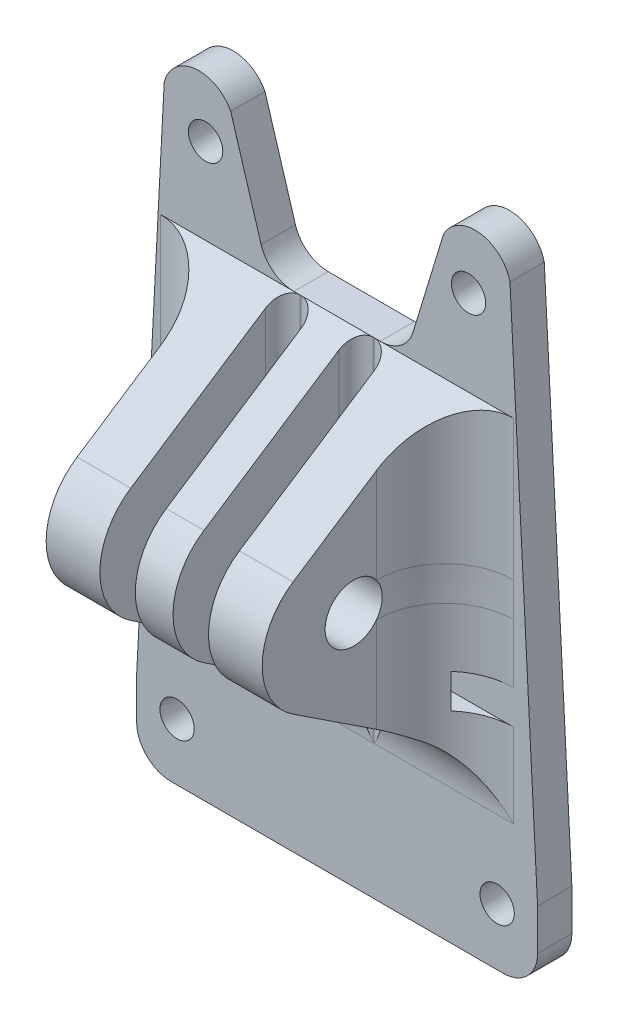
SolidWorks part; units mm, degrees
ref_plane "Alzado" through (0, 0, 0) normal (0, 0, 1) x (1, 0, 0)
ref_plane "Planta" through (0, 0, 0) normal (0, 1, 0) x (1, 0, 0)
ref_plane "Vista lateral" through (0, 0, 0) normal (1, 0, 0) x (0, 0, -1)
sketch "Croquis1" plane through (0, 0, 0) normal (0, 0, 1) x (1, 0, 0)
  line L0 (0, 0) -> (27.8544, 27.8544) construction
  line L1 (0, 0) -> (-42.4264, 42.4264) construction
  line L2 (0, 0) -> (0, 42.4264) construction
  line L3 (15.25, -15.25) -> (-15.25, -15.25) construction
  line L4 (15.25, -15.25) -> (15.25, 15.25) construction
  line L5 (15.25, 15.25) -> (-15.25, 15.25) construction
  line L6 (-15.25, -15.25) -> (-15.25, 15.25) construction
  line L7 (15.25, -15.25) -> (-15.25, 15.25) construction
  line L8 (15.25, 15.25) -> (-15.25, -15.25) construction
  line L9 (0, 42.4264) -> (-20, 42.4264) construction
  line L10 (-42.4264, 42.4264) -> (-38.8909, 45.9619) construction
  line L11 (-38.8909, 45.9619) -> (-31.0962, 38.1673) construction
  line L13 (-42.4264, 42.4264) -> (-45.9619, 38.8909) construction
  line L14 (-45.9619, 38.8909) -> (-38.1673, 31.0962) construction
  line L16 (38.8909, 45.9619) -> (31.0962, 38.1673) construction
  line L17 (42.4264, 42.4264) -> (38.8909, 45.9619) construction
  line L18 (42.4264, 42.4264) -> (45.9619, 38.8909) construction
  line L19 (-45.9619, -38.8909) -> (-38.1673, -31.0962) construction
  line L20 (0, 0) -> (-15.25, 0) construction
  line L21 (45.9619, 38.8909) -> (38.1673, 31.0962) construction
  line L22 (42.4264, -42.4264) -> (45.9619, -38.8909) construction
  line L23 (42.4264, -42.4264) -> (38.8909, -45.9619) construction
  line L24 (38.8909, -45.9619) -> (31.0962, -38.1673) construction
  line L27 (-38.8909, -45.9619) -> (-31.0962, -38.1673) construction
  line L28 (-42.4264, -42.4264) -> (-38.8909, -45.9619) construction
  line L29 (-42.4264, -42.4264) -> (-45.9619, -38.8909) construction
  line L30 (45.9619, -38.8909) -> (38.1673, -31.0962) construction
  line L31 (-15, 80) -> (15, 80) construction
  line L32 (0, -15.25) -> (0, -80) construction
  line L36 (-15, -80) -> (15, -80) construction
  line L41 (-12.268, -54) -> (-12.268, -67.5) construction
  line L43 (-10.268, -54) -> (-10.268, -67.5) construction
  line L105 (0, -80) -> (0, -83) construction
  line L106 (-15, -80) -> (0, -83) construction
  line L127 (15, -80) -> (0, -83) construction
  line L131 (0, 80) -> (0, 83) construction
  line L132 (-15, 80) -> (15, 80) construction
  line L136 (15, 80) -> (0, 83) construction
  line L157 (-15, 80) -> (0, 83) construction
  line L160 (-14, 30) -> (-17.8891, 33.8891) construction
  line L161 (-31.0962, 38.1673) -> (-22.6531, 29.7242) construction
  line L162 (-17.5359, 31.6883) -> (-15, 80) construction
  line L163 (17.5359, 31.6883) -> (15, 80) construction
  line L164 (31.0962, 38.1673) -> (22.6531, 29.7242) construction
  line L165 (31.0962, -38.1673) -> (22.6531, -29.7242) construction
  line L166 (17.5359, -31.6883) -> (15, -80) construction
  line L167 (-17.5359, -31.6883) -> (-15, -80) construction
  line L168 (-31.0962, -38.1673) -> (-22.6531, -29.7242) construction
  line L169 (-8.268, -54) -> (-8.268, -67.5) construction
  line L170 (-6.268, -54) -> (-6.268, -67.5) construction
  line L171 (-4.268, -54) -> (-4.268, -67.5) construction
  line L172 (-2.268, -54) -> (-2.268, -67.5) construction
  line L173 (-8.268, -35) -> (-8.268, -48.5) construction
  line L174 (-6.268, -35) -> (-6.268, -48.5) construction
  line L175 (-4.268, -35) -> (-4.268, -48.5) construction
  line L176 (-2.268, -35) -> (-2.268, -48.5) construction
  line L177 (-12.268, -35) -> (-12.268, -48.5) construction
  line L178 (-10.268, -35) -> (-10.268, -48.5) construction
  line L179 (10.268, -35) -> (10.268, -48.5) construction
  line L180 (12.268, -35) -> (12.268, -48.5) construction
  line L181 (2.268, -35) -> (2.268, -48.5) construction
  line L182 (4.268, -35) -> (4.268, -48.5) construction
  line L183 (6.268, -35) -> (6.268, -48.5) construction
  line L184 (8.268, -35) -> (8.268, -48.5) construction
  line L185 (2.268, -54) -> (2.268, -67.5) construction
  line L186 (4.268, -54) -> (4.268, -67.5) construction
  line L187 (6.268, -54) -> (6.268, -67.5) construction
  line L188 (8.268, -54) -> (8.268, -67.5) construction
  line L189 (10.268, -54) -> (10.268, -67.5) construction
  line L190 (12.268, -54) -> (12.268, -67.5) construction
  line L191 (12.268, 54) -> (12.268, 67.5) construction
  line L192 (10.268, 54) -> (10.268, 67.5) construction
  line L193 (8.268, 54) -> (8.268, 67.5) construction
  line L194 (6.268, 54) -> (6.268, 67.5) construction
  line L195 (4.268, 54) -> (4.268, 67.5) construction
  line L196 (2.268, 54) -> (2.268, 67.5) construction
  line L197 (8.268, 35) -> (8.268, 48.5) construction
  line L198 (6.268, 35) -> (6.268, 48.5) construction
  line L199 (4.268, 35) -> (4.268, 48.5) construction
  line L200 (2.268, 35) -> (2.268, 48.5) construction
  line L201 (12.268, 35) -> (12.268, 48.5) construction
  line L202 (10.268, 35) -> (10.268, 48.5) construction
  line L203 (-10.268, 35) -> (-10.268, 48.5) construction
  line L204 (-12.268, 35) -> (-12.268, 48.5) construction
  line L205 (-2.268, 35) -> (-2.268, 48.5) construction
  line L206 (-4.268, 35) -> (-4.268, 48.5) construction
  line L207 (-6.268, 35) -> (-6.268, 48.5) construction
  line L208 (-8.268, 35) -> (-8.268, 48.5) construction
  line L209 (-2.268, 54) -> (-2.268, 67.5) construction
  line L210 (-4.268, 54) -> (-4.268, 67.5) construction
  line L211 (-6.268, 54) -> (-6.268, 67.5) construction
  line L212 (-8.268, 54) -> (-8.268, 67.5) construction
  line L213 (-10.268, 54) -> (-10.268, 67.5) construction
  line L214 (-12.268, 54) -> (-12.268, 67.5) construction
  line L215 (-0.621, -15.7817) -> (-8.2129, -22.282) construction
  line L216 (-7.5625, -24.0416) -> (8.3607, -24.0416) construction
  line L217 (8.9758, -22.2532) -> (0.6445, -15.7529) construction
  line L218 (-7.5625, 24.0416) -> (8.3607, 24.0416) construction
  line L219 (8.9758, 22.2532) -> (0.6445, 15.7529) construction
  line L220 (-0.621, 15.7817) -> (-8.2129, 22.282) construction
  line L221 (-38.1673, 31.0962) -> (-28.2843, 21.2132) construction
  line L222 (-28.2843, -21.2132) -> (-38.1673, -31.0962) construction
  line L223 (28.2843, -21.2132) -> (38.1673, -31.0962) construction
  line L224 (38.1673, 31.0962) -> (28.2843, 21.2132) construction
  line L225 (-17.5359, 31.6883) -> (-15, 80)
  line L226 (-15, 80) -> (0, 83)
  line L227 (0, 83) -> (15, 80)
  line L228 (15, 80) -> (17.5359, 31.6883)
  line L229 (17.5359, 31.6883) -> (17.5359, -31.6883)
  line L230 (17.5359, -31.6883) -> (15, -80)
  line L231 (15, -80) -> (0, -83)
  line L232 (0, -83) -> (-15, -80)
  line L233 (-15, -80) -> (-17.5359, -31.6883)
  line L234 (-17.5359, -31.6883) -> (-17.5359, 31.6883)
  circle A0 centre (-15.25, 15.25) radius 4 construction
  circle A1 centre (-24.0416, 24.0416) radius 1.5 construction
  circle A2 centre (-38.8909, 38.8909) radius 1.5 construction
  circle A5 centre (38.8909, 38.8909) radius 1.5 construction
  circle A6 centre (24.0416, 24.0416) radius 1.5 construction
  circle A7 centre (15.25, 15.25) radius 4 construction
  circle A8 centre (15.25, -15.25) radius 4 construction
  circle A9 centre (24.0416, -24.0416) radius 1.5 construction
  circle A10 centre (38.8909, -38.8909) radius 1.5 construction
  circle A12 centre (-15.25, -15.25) radius 4 construction
  circle A13 centre (-24.0416, -24.0416) radius 1.5 construction
  circle A14 centre (-38.8909, -38.8909) radius 1.5 construction
  circle A18 centre (0, 0) radius 3.5 construction
  circle A19 centre (-11.5, -75) radius 1.5 construction
  circle A21 centre (-14, 30) radius 1.5 construction
  arc A27 (-12.268, -54) -> (-10.268, -54) centre (-11.268, -54) cw construction
  arc A28 (-12.268, -67.5) -> (-10.268, -67.5) centre (-11.268, -67.5) ccw construction
  circle A111 centre (11.5, -75) radius 1.5 construction
  circle A112 centre (11.5, 75) radius 1.5 construction
  circle A137 centre (-11.5, 75) radius 1.5 construction
  arc A138 (-22.6531, 29.7242) -> (-17.5359, 31.6883) centre (-20.5318, 31.8455) ccw construction
  arc A139 (22.6531, 29.7242) -> (17.5359, 31.6883) centre (20.5318, 31.8455) cw construction
  arc A140 (22.6531, -29.7242) -> (17.5359, -31.6883) centre (20.5318, -31.8455) ccw construction
  arc A141 (-22.6531, -29.7242) -> (-17.5359, -31.6883) centre (-20.5318, -31.8455) cw construction
  circle A142 centre (14, 30) radius 1.5 construction
  circle A143 centre (14, -30) radius 1.5 construction
  circle A144 centre (-14, -30) radius 1.5 construction
  arc A145 (-8.268, -67.5) -> (-6.268, -67.5) centre (-7.268, -67.5) ccw construction
  arc A146 (-8.268, -54) -> (-6.268, -54) centre (-7.268, -54) cw construction
  arc A147 (-4.268, -67.5) -> (-2.268, -67.5) centre (-3.268, -67.5) ccw construction
  arc A148 (-4.268, -54) -> (-2.268, -54) centre (-3.268, -54) cw construction
  arc A149 (-8.268, -48.5) -> (-6.268, -48.5) centre (-7.268, -48.5) ccw construction
  arc A150 (-8.268, -35) -> (-6.268, -35) centre (-7.268, -35) cw construction
  arc A151 (-4.268, -48.5) -> (-2.268, -48.5) centre (-3.268, -48.5) ccw construction
  arc A152 (-4.268, -35) -> (-2.268, -35) centre (-3.268, -35) cw construction
  arc A153 (-12.268, -48.5) -> (-10.268, -48.5) centre (-11.268, -48.5) ccw construction
  arc A154 (-12.268, -35) -> (-10.268, -35) centre (-11.268, -35) cw construction
  arc A155 (12.268, -35) -> (10.268, -35) centre (11.268, -35) ccw construction
  arc A156 (12.268, -48.5) -> (10.268, -48.5) centre (11.268, -48.5) cw construction
  arc A157 (4.268, -35) -> (2.268, -35) centre (3.268, -35) ccw construction
  arc A158 (4.268, -48.5) -> (2.268, -48.5) centre (3.268, -48.5) cw construction
  arc A159 (8.268, -35) -> (6.268, -35) centre (7.268, -35) ccw construction
  arc A160 (8.268, -48.5) -> (6.268, -48.5) centre (7.268, -48.5) cw construction
  arc A161 (4.268, -54) -> (2.268, -54) centre (3.268, -54) ccw construction
  arc A162 (4.268, -67.5) -> (2.268, -67.5) centre (3.268, -67.5) cw construction
  arc A163 (8.268, -54) -> (6.268, -54) centre (7.268, -54) ccw construction
  arc A164 (8.268, -67.5) -> (6.268, -67.5) centre (7.268, -67.5) cw construction
  arc A165 (12.268, -67.5) -> (10.268, -67.5) centre (11.268, -67.5) cw construction
  arc A166 (12.268, -54) -> (10.268, -54) centre (11.268, -54) ccw construction
  arc A167 (12.268, 54) -> (10.268, 54) centre (11.268, 54) cw construction
  arc A168 (12.268, 67.5) -> (10.268, 67.5) centre (11.268, 67.5) ccw construction
  arc A169 (8.268, 67.5) -> (6.268, 67.5) centre (7.268, 67.5) ccw construction
  arc A170 (8.268, 54) -> (6.268, 54) centre (7.268, 54) cw construction
  arc A171 (4.268, 67.5) -> (2.268, 67.5) centre (3.268, 67.5) ccw construction
  arc A172 (4.268, 54) -> (2.268, 54) centre (3.268, 54) cw construction
  arc A173 (8.268, 48.5) -> (6.268, 48.5) centre (7.268, 48.5) ccw construction
  arc A174 (8.268, 35) -> (6.268, 35) centre (7.268, 35) cw construction
  arc A175 (4.268, 48.5) -> (2.268, 48.5) centre (3.268, 48.5) ccw construction
  arc A176 (4.268, 35) -> (2.268, 35) centre (3.268, 35) cw construction
  arc A177 (12.268, 48.5) -> (10.268, 48.5) centre (11.268, 48.5) ccw construction
  arc A178 (12.268, 35) -> (10.268, 35) centre (11.268, 35) cw construction
  arc A179 (-12.268, 35) -> (-10.268, 35) centre (-11.268, 35) ccw construction
  arc A180 (-12.268, 48.5) -> (-10.268, 48.5) centre (-11.268, 48.5) cw construction
  arc A181 (-4.268, 35) -> (-2.268, 35) centre (-3.268, 35) ccw construction
  arc A182 (-4.268, 48.5) -> (-2.268, 48.5) centre (-3.268, 48.5) cw construction
  arc A183 (-8.268, 35) -> (-6.268, 35) centre (-7.268, 35) ccw construction
  arc A184 (-8.268, 48.5) -> (-6.268, 48.5) centre (-7.268, 48.5) cw construction
  arc A185 (-4.268, 54) -> (-2.268, 54) centre (-3.268, 54) ccw construction
  arc A186 (-4.268, 67.5) -> (-2.268, 67.5) centre (-3.268, 67.5) cw construction
  arc A187 (-8.268, 54) -> (-6.268, 54) centre (-7.268, 54) ccw construction
  arc A188 (-8.268, 67.5) -> (-6.268, 67.5) centre (-7.268, 67.5) cw construction
  arc A189 (-12.268, 67.5) -> (-10.268, 67.5) centre (-11.268, 67.5) cw construction
  arc A190 (-12.268, 54) -> (-10.268, 54) centre (-11.268, 54) ccw construction
  arc A191 (8.3607, -24.0416) -> (8.9758, -22.2532) centre (8.3607, -23.0416) ccw construction
  arc A192 (0.6445, -15.7529) -> (-0.621, -15.7817) centre (0.0294, -16.5413) ccw construction
  arc A193 (-8.2129, -22.282) -> (-7.5625, -24.0416) centre (-7.5625, -23.0416) ccw construction
  arc A194 (8.3607, 24.0416) -> (8.9758, 22.2532) centre (8.3607, 23.0416) cw construction
  arc A195 (0.6445, 15.7529) -> (-0.621, 15.7817) centre (0.0294, 16.5413) cw construction
  arc A196 (-8.2129, 22.282) -> (-7.5625, 24.0416) centre (-7.5625, 23.0416) cw construction
  arc A197 (-28.2843, 21.2132) -> (-28.2843, -21.2132) centre (-49.4975, 0) cw construction
  arc A198 (28.2843, 21.2132) -> (28.2843, -21.2132) centre (49.4975, 0) ccw construction
  circle A199 centre (-11.5, 75) radius 1.5
  circle A200 centre (11.5, 75) radius 1.5
  circle A201 centre (14, 30) radius 1.5
  circle A202 centre (-14, 30) radius 1.5
  circle A203 centre (-14, -30) radius 1.5
  circle A204 centre (14, -30) radius 1.5
  circle A205 centre (-11.5, -75) radius 1.5
  circle A206 centre (11.5, -75) radius 1.5
  point P35 (-34.9935, 42.0646)
  point P37 (44.1942, 40.6586)
  point P45 (44.1942, -40.6586)
  point P52 (-16.268, -55.8441)
  point P61 (-34.9935, -42.0646)
  point P70 (0, 80)
  point P260 (-7.0711, 0)
  dimension "D2" = 8
  dimension "D4" = 5
  dimension "D8" = 14.75
  dimension "D10" = 3
  dimension "D11" = 3
  dimension "D13" = 11.5
  dimension "D15" = 3
  dimension "D16" = 14
  dimension "D18" = 3
  dimension "D24" = 3
  dimension "D26" = 1
  dimension "D27" = 7
  dimension "D28" = 30
  dimension "D1" = 30.5
  dimension "D3" = 60
  dimension "D5" = 21
  dimension "D6" = 15
  dimension "D7" = 5
  dimension "D9" = 5
  dimension "D12" = 80
  dimension "D14" = 5
  dimension "D17" = 4
  dimension "D19" = 2
  dimension "D20" = 13.5
  dimension "D21" = 7.5
  dimension "D22" = 3
  dimension "D25" = 2
  dimension "D23" = 5.5
extrude "Saliente-Extruir1" add sketch "Croquis1" along normal blind 2
sketch "Croquis2" plane through (0, 0, 2) normal (0, 0, 1) x (1, 0, 0)
  line L1 (0, 83) -> (-15, 80) construction
  line L2 (-7.5, 81.5) -> (7.5, 81.5) construction
  line L3 (15, 80) -> (0, 83) construction
  line L4 (7.5, 81.5) -> (15, 80) construction
  line L5 (0, 81.5) -> (0, 67.5) construction
  line L6 (-10, 75) -> (-8.2794, 75) construction
  line L7 (-10.0971, 80.9806) -> (-8.2794, 75) construction
  line L8 (-10.0971, 80.9806) -> (-6, 67.5)
  line L9 (-6, 67.5) -> (6, 67.5)
  line L10 (-10.0971, 80.9806) -> (0, 83)
  line L11 (10.0971, 80.9806) -> (6, 67.5)
  line L12 (10.0971, 80.9806) -> (0, 83)
  line L13 (-10, 75) -> (-10, 65) construction
  line L14 (-10, 65) -> (-11.3105, 40.0344)
  line L15 (0, 67.5) -> (0, 30) construction
  line L16 (-10.6552, 52.5172) -> (0, 51.9579) construction
  line L17 (0, 51.9579) -> (-2, 52.0629) construction
  line L18 (0, 30) -> (0, 37.5) construction
  line L19 (-11.3105, 40.0344) -> (-2, 52.0629)
  line L20 (-2, 52.0629) -> (-10, 65)
  line L21 (2, 52.0629) -> (10, 65)
  line L22 (10, 65) -> (11.3105, 40.0344)
  line L23 (11.3105, 40.0344) -> (2, 52.0629)
  line L24 (-12.5, 30) -> (12.5, 30) construction
  line L25 (0, 37.5) -> (-7.5, 37.5) construction
  line L26 (0, 30) -> (-7.5, 37.5)
  line L27 (-7.5, 37.5) -> (0, 47.1895)
  line L28 (0, 30) -> (7.5, 37.5)
  line L29 (7.5, 37.5) -> (0, 47.1895)
  line L30 (-17.5359, 0) -> (17.5359, 0) construction
  line L31 (-17.5359, 31.6883) -> (-17.5359, -31.6883) construction
  line L32 (17.5359, -31.6883) -> (17.5359, 31.6883) construction
  line L33 (-10.5359, 18) -> (10.5359, 18)
  line L34 (-12.5, 25) -> (12.5, 25)
  line L35 (-12.5, 25) -> (-12.5, 22)
  line L36 (-12.5, 22) -> (12.5, 22)
  line L37 (12.5, 25) -> (12.5, 22)
  line L38 (-10.5359, -1.5) -> (-10.5359, 1.5)
  line L39 (-10.5359, 1.5) -> (10.5359, 1.5)
  line L40 (10.5359, 1.5) -> (10.5359, -1.5)
  line L41 (0, 1.5) -> (0, 4.5) construction
  line L42 (-10.5359, 18) -> (0, 4.5)
  line L43 (0, 4.5) -> (10.5359, 18)
  line L44 (0, -1.5) -> (0, -4.5) construction
  line L45 (0, -37.5) -> (-7.5, -37.5) construction
  line L46 (-12.5, -30) -> (12.5, -30) construction
  line L47 (0, -30) -> (0, -37.5) construction
  line L48 (0, -51.9579) -> (-2, -52.0629) construction
  line L49 (-10.6552, -52.5172) -> (0, -51.9579) construction
  line L50 (0, -67.5) -> (0, -30) construction
  line L51 (-10, -75) -> (-10, -65) construction
  line L52 (-10.0971, -80.9806) -> (-8.2794, -75) construction
  line L53 (-10, -75) -> (-8.2794, -75) construction
  line L54 (0, -81.5) -> (0, -67.5) construction
  line L55 (7.5, -81.5) -> (15, -80) construction
  line L56 (-7.5, -81.5) -> (7.5, -81.5) construction
  line L57 (-15, -80) -> (-7.5, -81.5) construction
  line L58 (0, -4.5) -> (10.5359, -18)
  line L59 (-10.5359, -18) -> (0, -4.5)
  line L60 (-10.5359, -1.5) -> (10.5359, -1.5)
  line L61 (12.5, -25) -> (12.5, -22)
  line L62 (-12.5, -22) -> (12.5, -22)
  line L63 (-12.5, -25) -> (-12.5, -22)
  line L64 (-12.5, -25) -> (12.5, -25)
  line L65 (-10.5359, -18) -> (10.5359, -18)
  line L66 (7.5, -37.5) -> (0, -47.1895)
  line L67 (0, -30) -> (7.5, -37.5)
  line L68 (-7.5, -37.5) -> (0, -47.1895)
  line L69 (0, -30) -> (-7.5, -37.5)
  line L70 (11.3105, -40.0344) -> (2, -52.0629)
  line L71 (10, -65) -> (11.3105, -40.0344)
  line L72 (2, -52.0629) -> (10, -65)
  line L73 (-2, -52.0629) -> (-10, -65)
  line L74 (-11.3105, -40.0344) -> (-2, -52.0629)
  line L75 (-10, -65) -> (-11.3105, -40.0344)
  line L76 (10.0971, -80.9806) -> (0, -83)
  line L77 (10.0971, -80.9806) -> (6, -67.5)
  line L78 (-10.0971, -80.9806) -> (0, -83)
  line L79 (-6, -67.5) -> (6, -67.5)
  line L80 (-10.0971, -80.9806) -> (-6, -67.5)
  circle A0 centre (-11.5, 75) radius 1.5 construction
  circle A1 centre (-14, 30) radius 1.5 construction
  circle A2 centre (14, 30) radius 1.5 construction
  point P85 (10.5359, 0)
  point P86 (-10.5359, 0)
  dimension "D1" = 14
  dimension "D2" = 10
  dimension "D3" = 25
  dimension "D4" = 2
  dimension "D5" = 7.5
  dimension "D6" = 5
  dimension "D7" = 3
  dimension "D8" = 4
  dimension "D9" = 1.5
  dimension "D10" = 7
  dimension "D11" = 7
  dimension "D12" = 3
  dimension "D13" = 6
  dimension "D14" = 5
extrude "Cortar-Extruir1" cut sketch "Croquis2" against normal up to vertex (2 mm away) up to point (-17.5359, -31.6883, 0)
fillet "Redondeo2" radius 1 38 edges at (0, -30, 1) (11.3105, -40.0344, 1) (10, -65, 1) (2, -52.0629, 1) (-10, -65, 1) (-7.5, -37.5, 1) (7.5, -37.5, 1) (-2, -52.0629, 1) (-11.3105, -40.0344, 1) (12.5, 22, 1) (-12.5, 22, 1) (-12.5, 25, 1) (12.5, 25, 1) (10.5359, 18, 1) (-10.5359, 18, 1) (0, 4.5, 1) (10.5359, -1.5, 1) (-10.5359, -1.5, 1) (10.5359, 1.5, 1) (-10.5359, 1.5, 1) (10.5359, -18, 1) (0, -4.5, 1) (-10.5359, -18, 1) (12.5, -25, 1) (-12.5, -25, 1) (12.5, -22, 1) (-12.5, -22, 1) (0, 30, 1) (7.5, 37.5, 1) (-7.5, 37.5, 1) (0, 47.1895, 1) (11.3105, 40.0344, 1) (10, 65, 1) (2, 52.0629, 1) (-2, 52.0629, 1) (-11.3105, 40.0344, 1) (-10, 65, 1) (0, -47.1895, 1)
fillet "Redondeo1" radius 3 16 edges at (15, -80, 1) (-15, -80, 1) (15, 80, 1) (-15, 80, 1) (-6, -67.5, 1) (6, -67.5, 1) (10.0971, -80.9806, 1) (-10.0971, -80.9806, 1) (10.0971, 80.9806, 1) (6, 67.5, 1) (-6, 67.5, 1) (-10.0971, 80.9806, 1) (17.5359, -31.6883, 1) (17.5359, 31.6883, 1) (-17.5359, -31.6883, 1) (-17.5359, 31.6883, 1)
sketch "Croquis3" plane through (0, 0, 2) normal (0, 0, 1) x (1, 0, 0)
  line L0 (-17.5359, 31.6096) -> (-15.1222, 77.6726)
  line L1 (-9.306, 78.3777) -> (-6.6466, 69.6276)
  line L2 (3.7763, 67.5) -> (-3.7763, 67.5)
  line L3 (-3.7763, 67.5) -> (3.7763, 67.5) construction
  line L4 (14.5359, 25) -> (-14.5359, 25)
  line L5 (11.5, 25) -> (-11.5, 25) construction
  line L6 (-17.5359, 31.6096) -> (-17.5359, -31.6096) construction
  line L7 (-17.5359, 28) -> (-17.5359, 31.6096)
  line L8 (0, 67.5) -> (0, 25) construction
  line L9 (17.5359, 28) -> (17.5359, 31.6096)
  line L10 (9.306, 78.3777) -> (6.6466, 69.6276)
  line L11 (17.5359, 31.6096) -> (15.1222, 77.6726)
  arc A0 (-15.1222, 77.6726) -> (-9.306, 78.3777) centre (-12.0835, 76.9476) cw
  arc A1 (-6.6466, 69.6276) -> (-3.7763, 67.5) centre (-3.7763, 70.5) ccw
  circle A2 centre (-11.5, 75) radius 1.5
  circle A3 centre (-14, 30) radius 1.5
  circle A4 centre (14, 30) radius 1.5
  circle A5 centre (11.5, 75) radius 1.5
  arc A6 (6.6466, 69.6276) -> (3.7763, 67.5) centre (3.7763, 70.5) cw
  arc A7 (15.1222, 77.6726) -> (9.306, 78.3777) centre (12.0835, 76.9476) ccw
  arc A8 (17.5359, 28) -> (14.5359, 25) centre (14.5359, 28) cw
  arc A9 (-14.5359, 25) -> (-17.5359, 28) centre (-14.5359, 28) cw
  point P41 (17.5359, 25)
  point P44 (-17.5359, 25)
  dimension "D1" = 3
extrude "Saliente-Extruir2" add sketch "Croquis3" along normal blind 3
sketch "Croquis4" plane through (0, 0, 2) normal (0, 0, 1) x (1, 0, 0)
  line L1 (-41.3462, 95.3241) -> (47.8508, 95.3241)
  line L2 (-41.3462, 95.3241) -> (-41.3462, -93.5853)
  line L3 (-41.3462, -93.5853) -> (47.8508, -93.5853)
  line L4 (47.8508, 95.3241) -> (47.8508, -93.5853)
extrude "Cortar-Extruir2" cut sketch "Croquis4" against normal up to vertex (2 mm away) up to point (-17.5318, -31.7668, 0)
ref_plane "Plano1" through (0, 0, 0) normal (1, 0, 0) x (0, 0, -1)
sketch "Croquis5" plane through (0, 0, 0) normal (1, 0, 0) x (0, 0, -1)
  line L0 (-5, 67.5) -> (-18.2954, 58.762)
  line L1 (-18.2954, 48.7339) -> (-5, 39.9958)
  line L2 (-5, 77.6726) -> (-5, 31.6096) construction
  line L3 (-5, 39.9958) -> (-5, 67.5)
  line L4 (-5, 53.7479) -> (-33.5242, 53.7479) construction
  line L5 (-18.5, 53.7479) -> (-21, 53.7479) construction
  circle A0 centre (-13, 53.7479) radius 2.5
  arc A1 (-18.2954, 58.762) -> (-18.2954, 48.7339) centre (-15, 53.7479) ccw
  circle A2 centre (-13, 53.7479) radius 5.5 construction
  point P13 (-25.9245, 53.7479)
  dimension "D1" = 5
  dimension "D3" = 6
  dimension "D4" = 2.5
  dimension "D5" = 11
  dimension "D2" = 8
extrude "Saliente-Extruir3" add sketch "Croquis5" along normal blind 1.65 and the other way blind 1.65
ref_plane "Plano2" through (4.75, 0, 0) normal (1, 0, 0) x (0, 0, -1)
ref_plane "Plano3" through (-4.75, 0, 0) normal (-1, 0, 0) x (0, 0, 1)
extrude "Saliente-Extruir4" add sketch "Croquis5<2>" along normal blind 4.7 from surface starting at plane "Plano2"
sketch "Croquis5<2>" plane through (0, 0, 0) normal (1, 0, 0) x (0, 0, -1) same geometry as "Croquis5"
extrude "Saliente-Extruir5" add sketch "Croquis5<3>" against normal blind 4.7 from surface starting at plane "Plano3"
sketch "Croquis5<3>" plane through (0, 0, 0) normal (1, 0, 0) x (0, 0, -1) same geometry as "Croquis5"
fillet "Redondeo3" radius 1.5 4 edges at (-4.75, 53.7479, 5) (-1.65, 53.7479, 5) (1.65, 53.7479, 5) (4.75, 53.7479, 5)
fillet "Redondeo4" radius 6 5 edges at (6.35, 39.9958, 5) (0, 39.9958, 5) (-6.35, 39.9958, 5) (9.45, 53.7479, 5) (-9.45, 53.7479, 5)
sketch "Croquis6" plane through (9.45, 0, 0) normal (1, 0, 0) x (0, 0, -1)
  circle A0 centre (-13, 53.7479) radius 5.5
  circle A1 centre (-13, 53.7479) radius 2.5
  dimension "D1" = 11
sketch "Croquis7" plane through (-9.45, 0, 0) normal (-1, 0, 0) x (0, 0, 1)
  line L1 (14.8353, 49.5094) -> (17.5883, 53.2181)
  line L2 (17.5883, 53.2181) -> (15.753, 57.4566)
  line L3 (15.753, 57.4566) -> (11.1647, 57.9864)
  line L4 (11.1647, 57.9864) -> (8.4117, 54.2777)
  line L5 (8.4117, 54.2777) -> (10.247, 50.0392)
  line L6 (10.247, 50.0392) -> (14.8353, 49.5094)
  circle A0 centre (13, 53.7479) radius 4 construction
  dimension "D1" = 8
extrude "Cortar-Extruir3" cut sketch "Croquis7" against normal blind 3.5 and the other way blind 10
sketch "Croquis8" plane through (-9.45, 0, 0) normal (-1, 0, 0) x (0, 0, 1)
  line L0 (16.4412, 58.3838) -> (17.3353, 59.5882) construction
  line L1 (15.2942, 48.4498) -> (18.7354, 53.0856)
  line L2 (18.7354, 53.0856) -> (16.4412, 58.3838)
  line L3 (16.4412, 58.3838) -> (10.7058, 59.046)
  line L4 (10.7058, 59.046) -> (7.2646, 54.4102)
  line L5 (7.2646, 54.4102) -> (9.5588, 49.112)
  line L6 (9.5588, 49.112) -> (15.2942, 48.4498)
  circle A0 centre (13, 53.7479) radius 5 construction
  circle A1 centre (13, 53.7479) radius 7.2735
  dimension "D1" = 1.5
sketch "Croquis9" plane through (-5.95, 0, 0) normal (-1, 0, 0) x (0, 0, 1)
  line L0 (5, 77.6726) -> (5, 31.6096) construction
  line L1 (5, 47.0996) -> (6.5, 47.0996)
  line L2 (5, 47.0996) -> (5, 44.0996)
  line L3 (5, 44.0996) -> (6.5, 44.0996)
  line L4 (6.5, 47.0996) -> (6.5, 44.0996)
  dimension "D1" = 3
  dimension "D2" = 1.5
extrude "Cortar-Extruir4" cut sketch "Croquis9" against normal up to vertex (23.4859 mm away) and the other way up to vertex (11.5859 mm away) up to point (17.5359, 28, 5) other way up to point (-17.5359, 28, 5)
